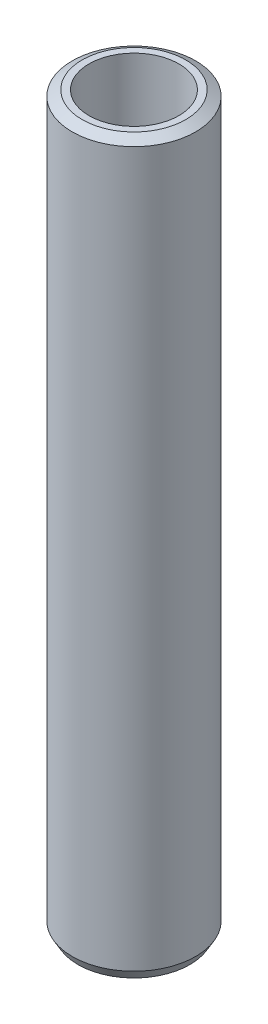
SolidWorks part; units mm, degrees
ref_plane "Front Plane" through (0, 0, 0) normal (0, 0, 1) x (1, 0, 0)
ref_plane "Top Plane" through (0, 0, 0) normal (0, 1, 0) x (1, 0, 0)
ref_plane "Right Plane" through (0, 0, 0) normal (1, 0, 0) x (0, 0, -1)
sketch "Sketch1" plane through (0, 0, 0) normal (0, 1, 0) x (1, 0, 0)
  circle A0 centre (0, 0) radius 50
  dimension "SHAFT_OD" = 100
extrude "Boss-Extrude1" add sketch "Sketch1" along normal blind 591.6617
sketch "Sketch2" plane through (0, 0, 0) normal (0, 1, 0) x (1, 0, 0)
  circle A0 centre (0, 0) radius 36.4171
  dimension "BORE_D" = 72.8343
extrude "Cut-Extrude1" cut sketch "Sketch2" along normal through all
chamfer "Chamfer1" distance 4.6287 angle 60 2 edges at (0, 591.6617, 50) (0, 0, 50) first distance on face at (0, 591.6617, 50) first distance on face at (0, 0, 36.4171)
